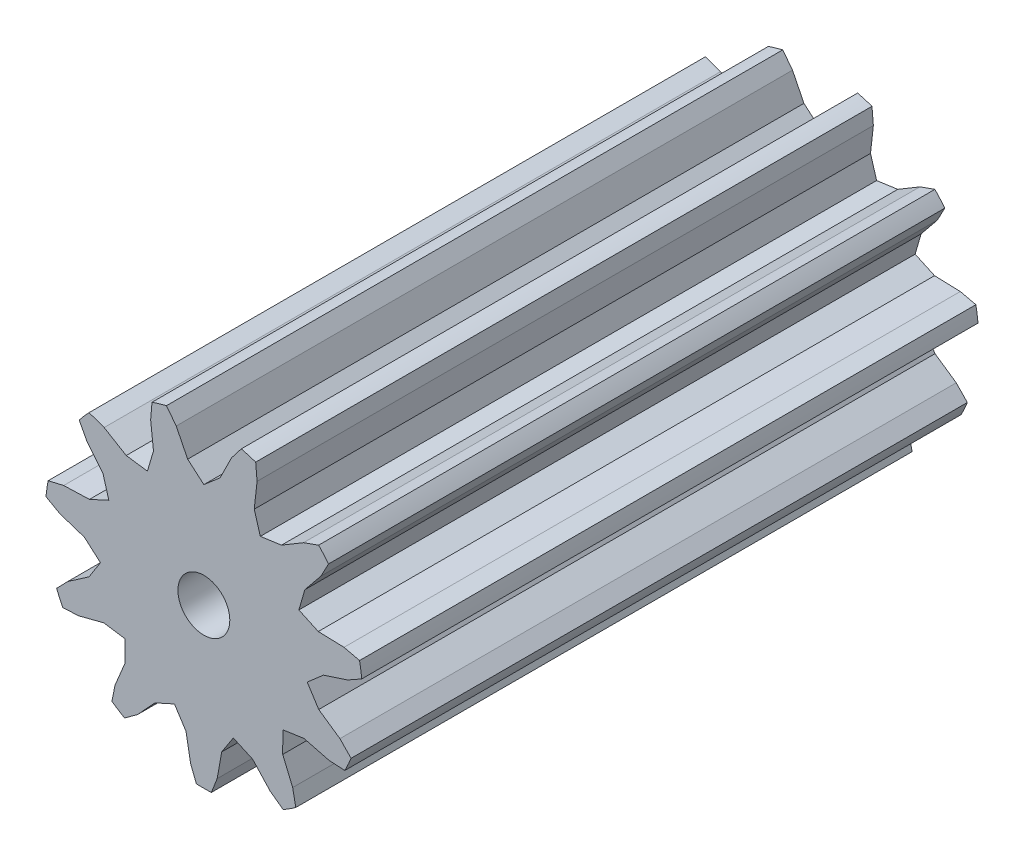
SolidWorks part; units mm, degrees
ref_plane "Front Plane" through (0, 0, 0) normal (0, 0, 1) x (1, 0, 0)
ref_plane "Top Plane" through (0, 0, 0) normal (0, 1, 0) x (1, 0, 0)
ref_plane "Right Plane" through (0, 0, 0) normal (1, 0, 0) x (0, 0, -1)
sketch "Sketch1" plane through (0, 0, 0) normal (0, 0, 1) x (1, 0, 0)
  line L1 (1.2374, -1.2374) -> (-1.2374, -1.2374) construction
  line L2 (1.2374, -1.2374) -> (1.2374, 1.2374) construction
  line L3 (1.2374, 1.2374) -> (-1.2374, 1.2374) construction
  line L4 (-1.2374, -1.2374) -> (-1.2374, 1.2374) construction
  line L5 (1.2374, -1.2374) -> (-1.2374, 1.2374) construction
  line L6 (1.2374, 1.2374) -> (-1.2374, -1.2374) construction
  circle A0 centre (0, 0) radius 9.7778
  circle A1 centre (0, 0) radius 1.75 construction
  dimension "D1" = 19.5556
  dimension "D2" = 3.5
extrude "Boss-Extrude1" add sketch "Sketch1" along normal blind 38
sketch "Sketch2" plane through (0, 0, 0) normal (0, 0, 1) x (1, 0, 0)
  line L0 (0, 0) -> (0, 10.088) construction
  line L1 (0, 6.4402) -> (-0.9985, 7.2997)
  line L8 (-1.7043, 10.285) -> (0, 10.9993)
  line L11 (-0.9985, 7.2997) -> (-1.7043, 8.7207)
  line L12 (-1.7043, 8.7207) -> (-2.3066, 9.5018)
  line L13 (-2.3066, 9.5018) -> (-1.7043, 10.285)
  line L14 (2.3066, 9.5018) -> (1.7043, 10.285)
  line L15 (1.7043, 8.7207) -> (2.3066, 9.5018)
  line L16 (0.9985, 7.2997) -> (1.7043, 8.7207)
  line L17 (1.7043, 10.285) -> (0, 10.9993)
  line L18 (0, 6.4402) -> (0.9985, 7.2997)
  circle A14 centre (0, 0) radius 9.7778 construction
  point P16 (0, 9.7778)
  dimension "D5" = 0.6023
  dimension "D6" = 0.7811
  dimension "D1" = 0.9985
  dimension "D2" = 0.8594
  dimension "D3" = 0.7058
  dimension "D4" = 1.4211
  dimension "D7" = 0.7832
  dimension "D8" = 0.6023
  dimension "D9" = 0.7142
  dimension "D10" = 1.7043
extrude "Cut-Extrude1" cut sketch "Sketch2" along normal through all
sketch "Sketch3" plane through (0, 0, 0) normal (0, 0, 1) x (1, 0, 0)
  circle A0 centre (0, 0) radius 7.5
  dimension "D1" = 15
sketch "Sketch4" plane through (0, 0, 38) normal (0, 0, 1) x (1, 0, 0)
  circle A0 centre (0, 0) radius 1.6
  dimension "D1" = 3.2
extrude "Cut-Extrude2" cut sketch "Sketch4" against normal through all both and the other way through all
pattern_circular "CirPattern1" count 11 over 360 about axis through (0, 0, 38) along (0, 0, -1) of "Cut-Extrude1" reverse direction yes
sketch "Sketch5" plane through (0, 0, 0) normal (0, 0, 1) x (1, 0, 0)
  line L0 (0, 0) -> (0, 16.5734) construction
  arc A0 (0, 2.7703) -> (-2.7395, 5.5802) centre (3.9333, 9.3453) cw
  arc A1 (-2.7395, 5.5802) -> (0, 7.0858) centre (3.4783, -2.4876) cw
  arc A2 (2.7395, 5.5802) -> (0, 7.0858) centre (-3.4783, -2.4876) ccw
  arc A3 (0, 2.7703) -> (2.7395, 5.5802) centre (-3.9333, 9.3453) ccw
equation "\"circle\"=19.5556"
equation "\"D1@Sketch1\"=\"circle\""
equation "\"separator_width\"=45"
equation "\"big-gear-thiccness\"=2"
equation "\"D1@Boss-Extrude1\"=\"separator_width\" - \"big-gear-thiccness\"-10/2"
